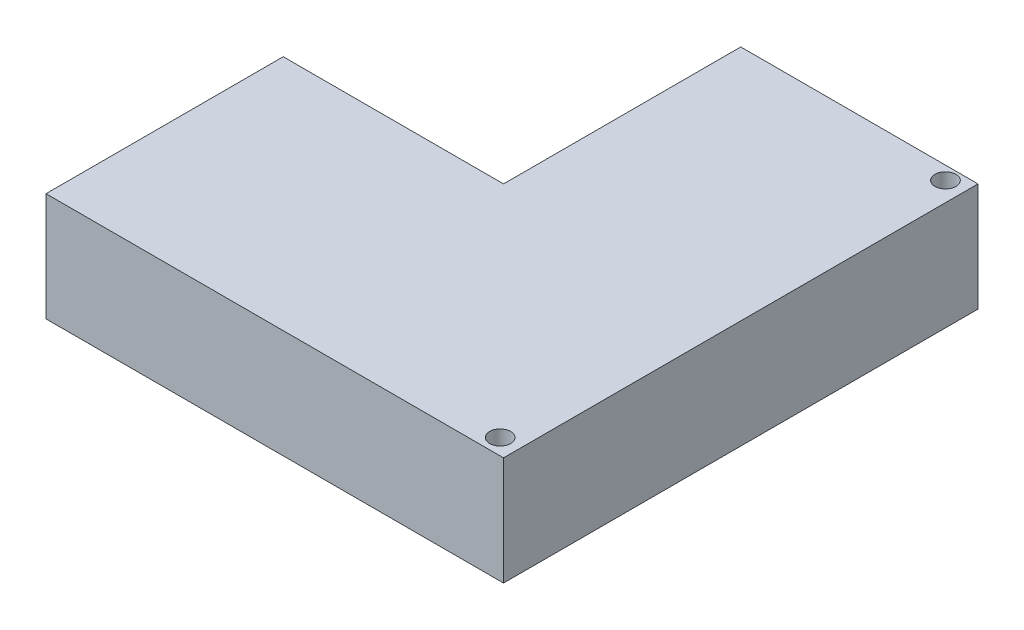
SolidWorks part; units mm, degrees
ref_plane "Front Plane" through (0, 0, 0) normal (0, 0, 1) x (1, 0, 0)
ref_plane "Top Plane" through (0, 0, 0) normal (0, 1, 0) x (1, 0, 0)
ref_plane "Right Plane" through (0, 0, 0) normal (1, 0, 0) x (0, 0, -1)
sketch "Sketch2" plane through (0, 0, 0) normal (0, -1, 0) x (1, 0, 0)
  line L0 (-13.7962, 46.5082) -> (-13.7962, -23.4918)
  line L1 (-13.7962, 46.5082) -> (-104.2962, 46.5082)
  line L2 (-13.7962, -23.4918) -> (-48.7962, -23.4918)
  line L4 (-104.2962, 46.5082) -> (-104.2962, 11.5082)
  line L5 (-104.2962, 11.5082) -> (-48.7962, 11.5082)
  line L6 (-48.7962, 11.5082) -> (-48.7962, -23.4918)
  dimension "D1" = 70
  dimension "D2" = 90.5
  dimension "D3" = 35
  dimension "D4" = 35
extrude "Boss-Extrude1" add sketch "Sketch2" along normal mid plane 16
other "Move Face1" flip direction yes face at (-104.2962, 0, 29.0082) offset 23 parameters "D1"=23
sketch "Sketch3" plane through (0, -8, 0) normal (0, -1, 0) x (1, 0, 0)
  line L2 (-13.7962, -23.4918) -> (-13.7962, 46.5082) construction
  line L5 (-13.7962, 46.5082) -> (-81.2962, 46.5082) construction
  line L7 (-48.7962, -23.4918) -> (-13.7962, -23.4918) construction
  circle A0 centre (-16.6462, 44.1582) radius 1.55
  circle A1 centre (-16.6462, -21.5418) radius 1.55
  point P4 (0, 0)
  point P5 (-16.6503, 43.8138)
  dimension "D1" = 3.1
  dimension "D2" = 1.3
  dimension "D3" = 0.8
  dimension "D4" = 0.4
extrude "Cut-Extrude1" cut sketch "Sketch3" against normal through all
